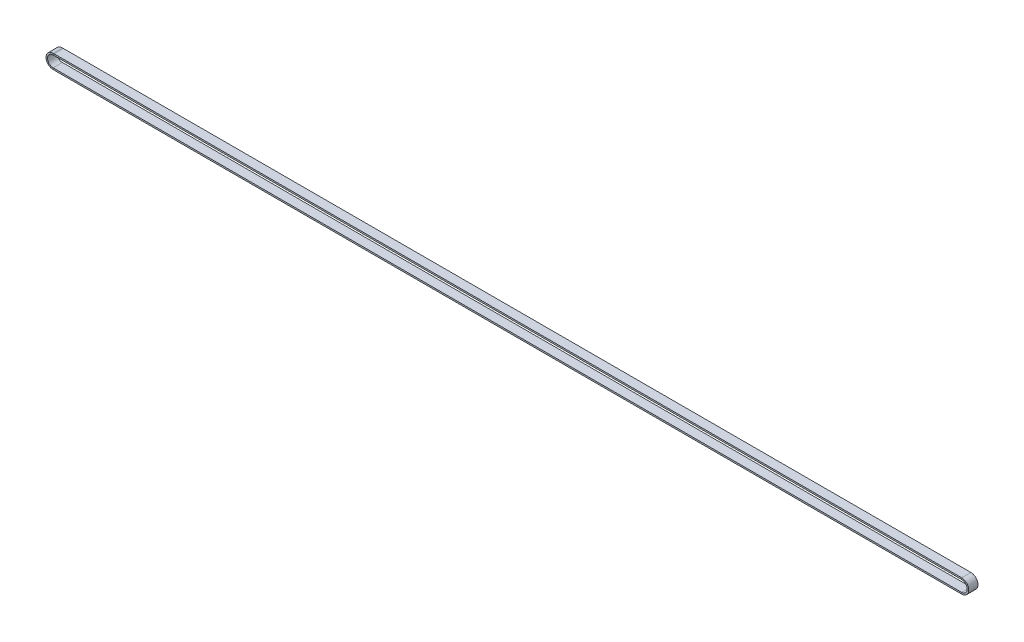
SolidWorks part; units mm, degrees
ref_plane "Front Plane" through (0, 0, 0) normal (0, 0, 1) x (1, 0, 0)
ref_plane "Top Plane" through (0, 0, 0) normal (0, 1, 0) x (1, 0, 0)
ref_plane "Right Plane" through (0, 0, 0) normal (1, 0, 0) x (0, 0, -1)
sketch "Sketch2" plane through (0, 0, -34.9834) normal (0, 0, 1) x (1, 0, 0)
  line L0 (0, 0) -> (1, 0) construction
  line L1 (0, 0) -> (0, 1) construction
  line L2 (-1, -57.8902) -> (883.5206, -57.8902)
  line L3 (883.5206, -71.6902) -> (-1, -71.6902)
  arc A0 (-1, -71.6902) -> (-1, -57.8902) centre (-1, -64.7902) cw
  arc A1 (883.5206, -57.8902) -> (883.5206, -71.6902) centre (883.5206, -64.7902) cw
sketch "Sketch3" plane through (0, 0, 0) normal (1, 0, 0) x (0, 0, -1)
  line L1 (34.9834, -59.3902) -> (25.9834, -59.3902)
  line L2 (34.9834, -59.3902) -> (34.9834, -57.8902)
  line L3 (34.9834, -57.8902) -> (25.9834, -57.8902)
  line L4 (25.9834, -59.3902) -> (25.9834, -57.8902)
  dimension "D1" = 9
  dimension "D2" = 1.5
sweep "Sweep1" add profiles "Sketch3" path "Sketch2"
